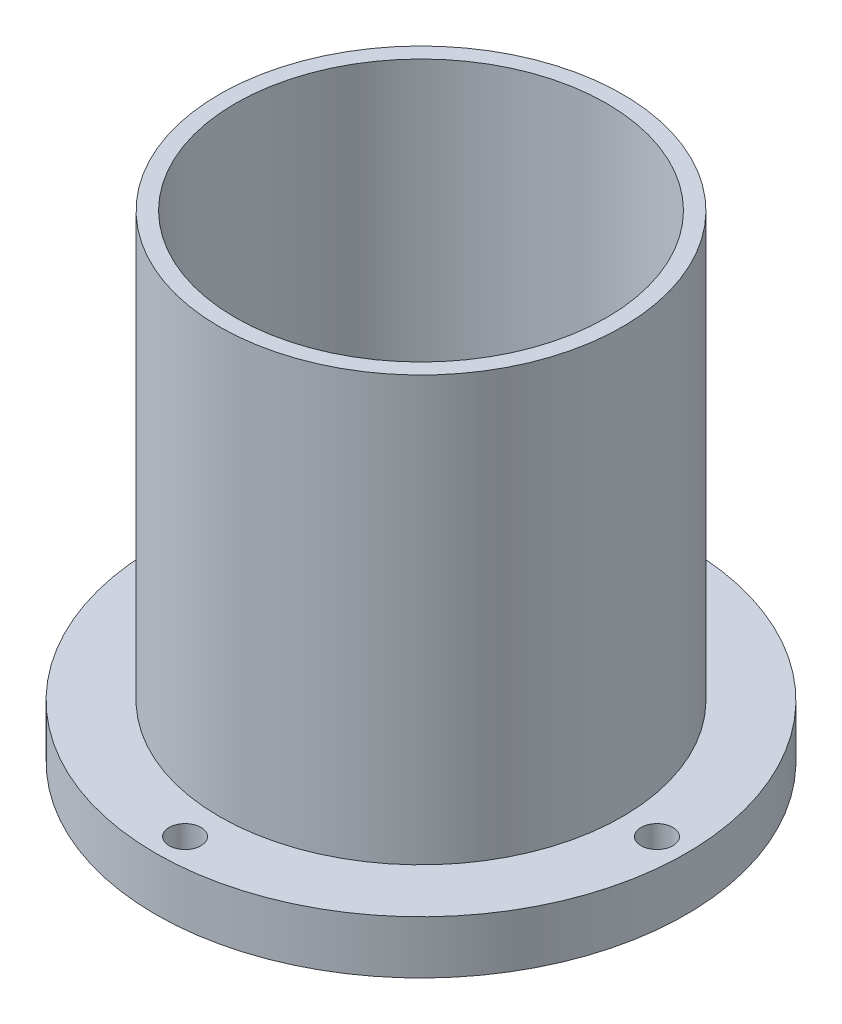
SolidWorks part; units mm, degrees
ref_plane "Front Plane" through (0, 0, 0) normal (0, 0, 1) x (1, 0, 0)
ref_plane "Top Plane" through (0, 0, 0) normal (0, 1, 0) x (1, 0, 0)
ref_plane "Right Plane" through (0, 0, 0) normal (1, 0, 0) x (0, 0, -1)
sketch "Sketch1" plane through (0, 0, 0) normal (0, 1, 0) x (1, 0, 0)
  circle A0 centre (0, 0) radius 50
  dimension "D1" = 100
extrude "Boss-Extrude1" add sketch "Sketch1" along normal blind 10
sketch "Sketch2" plane through (0, 10, 0) normal (0, 1, 0) x (1, 0, 0)
  circle A0 centre (0, 0) radius 44.5 construction
  circle A1 centre (-44.5, 0) radius 3
  circle A5 centre (0, 44.5) radius 3
  circle A6 centre (44.5, 0) radius 3
  circle A7 centre (0, -44.5) radius 3
  point P14 (4, 0)
  point P15 (0, 0)
  dimension "D1" = 89
  dimension "D2" = 6
  dimension "D3" = 4
extrude "Cut-Extrude1" cut sketch "Sketch2" against normal blind 10
sketch "Sketch3" plane through (0, 10, 0) normal (0, 1, 0) x (1, 0, 0)
  circle A0 centre (0, 0) radius 38
  circle A1 centre (0, 0) radius 35
  dimension "D1" = 76
  dimension "D2" = 70
extrude "Boss-Extrude2" add sketch "Sketch3" along normal blind 80
